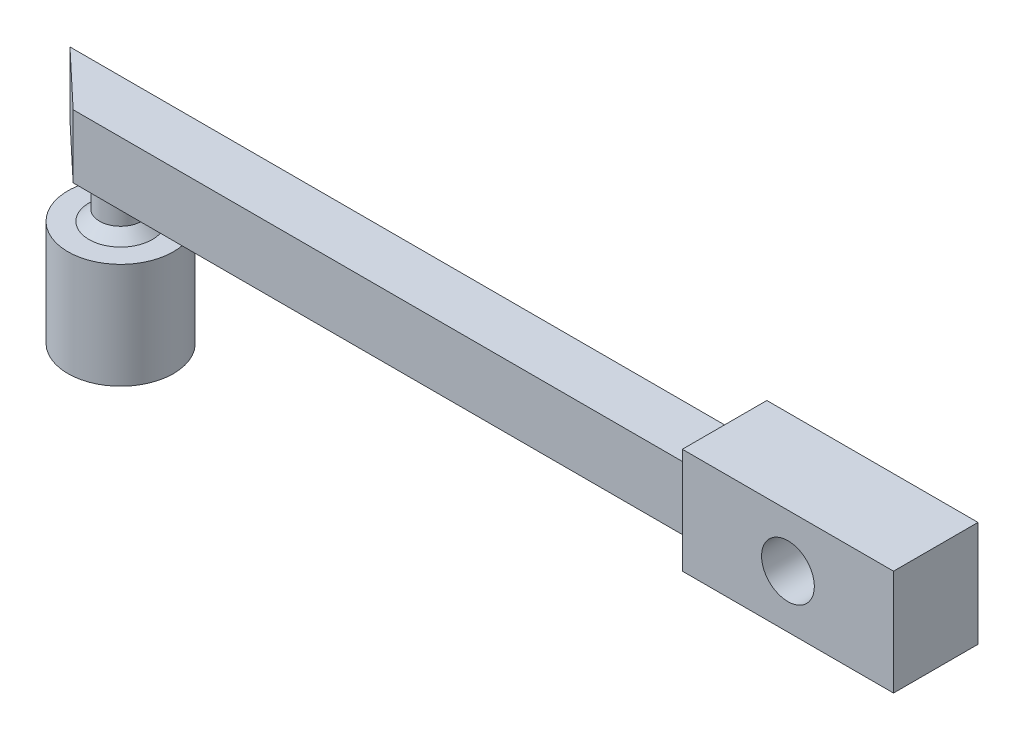
SolidWorks part; units mm, degrees
ref_plane "Piano frontale" through (0, 0, 0) normal (0, 0, 1) x (1, 0, 0)
ref_plane "Piano superiore" through (0, 0, 0) normal (0, 1, 0) x (1, 0, 0)
ref_plane "Piano destro" through (0, 0, 0) normal (1, 0, 0) x (0, 0, -1)
sketch "Schizzo1" plane through (0, 0, 0) normal (0, 0, 1) x (1, 0, 0)
  line L1 (16.5, -1.5) -> (-16.5, -1.5)
  line L2 (16.5, -1.5) -> (16.5, 1.5)
  line L3 (16.5, 1.5) -> (-16.5, 1.5)
  line L4 (-16.5, -1.5) -> (-16.5, 1.5)
  line L5 (16.5, -1.5) -> (-16.5, 1.5) construction
  line L6 (16.5, 1.5) -> (-16.5, -1.5) construction
  point P0 (0, 0)
  dimension "D1" = 3
  dimension "D2" = 33
extrude "Estrusione-Estrusione1" add sketch "Schizzo1" along normal blind 2.5
sketch "Schizzo2" plane through (0, -1.5, 0) normal (0, -1, 0) x (1, 0, 0)
  line L0 (-16.5, 0) -> (-13.85, 2.5)
  line L1 (-16.5, 2.5) -> (16.5, 2.5) construction
  line L2 (-13.85, 2.5) -> (-16.5, 2.5)
  line L3 (-16.5, 2.5) -> (-16.5, 0) construction
  line L4 (-16.5, 2.5) -> (-16.5, 0)
  dimension "D1" = 2.65
extrude "Taglio-Estrusione1" cut sketch "Schizzo2" against normal through all
sketch "Schizzo3" plane through (0, -1.5, 0) normal (0, -1, 0) x (1, 0, 0)
  line L0 (-13.85, 2.5) -> (-13.85, 0) construction
  line L1 (-16.5, 0) -> (16.5, 0) construction
  line L2 (-13.85, 1.25) -> (-12.85, 1.25) construction
  circle A0 centre (-12.85, 1.25) radius 1
  point P9 (0, 0)
  dimension "D1" = 2
  dimension "D2" = 1
extrude "Estrusione-Estrusione2" add sketch "Schizzo3" along normal blind 1.7
sketch "Schizzo5" plane through (0, -3.2, 0) normal (0, -1, 0) x (1, 0, 0)
  circle A0 centre (-12.85, 1.25) radius 2.5
  dimension "D1" = 5
extrude "Estrusione-Estrusione3" add sketch "Schizzo5" along normal blind 5
chamfer "Smusso2" distance 0.5 angle 45 1 edges at (-11.85, -3.2, 1.25)
sketch "Schizzo8" plane through (16.5, 0, 0) normal (1, 0, 0) x (0, 0, -1)
  line L0 (-2.5, -1.5) -> (0, -1.5) construction
  line L1 (-4, -1.5) -> (0, -1.5)
  line L2 (-4, -1.5) -> (-4, 3.5)
  line L3 (-4, 3.5) -> (0, 3.5)
  line L4 (0, -1.5) -> (0, 3.5)
  line L5 (-4, -1.5) -> (0, 3.5) construction
  line L6 (-4, 3.5) -> (0, -1.5) construction
  line L7 (0, -1.5) -> (0, 1.5) construction
  point P0 (-2, 1)
  dimension "D1" = 4
  dimension "D2" = 5
extrude "Estrusione-Estrusione6" add sketch "Schizzo8" along normal blind 10
sketch "Schizzo9" plane through (0, 0, 4) normal (0, 0, 1) x (1, 0, 0)
  line L0 (16.5, 3.5) -> (26.5, -1.5)
  circle A0 centre (21.5, 1) radius 1.25
  point P6 (0, 0)
  dimension "D1" = 2.5
extrude "Taglio-Estrusione3" cut sketch "Schizzo9" against normal through all contours L0 A0 | L0 A0 region at (21.7373, 1.4745, 4) region at (21.2627, 0.5255, 4)
